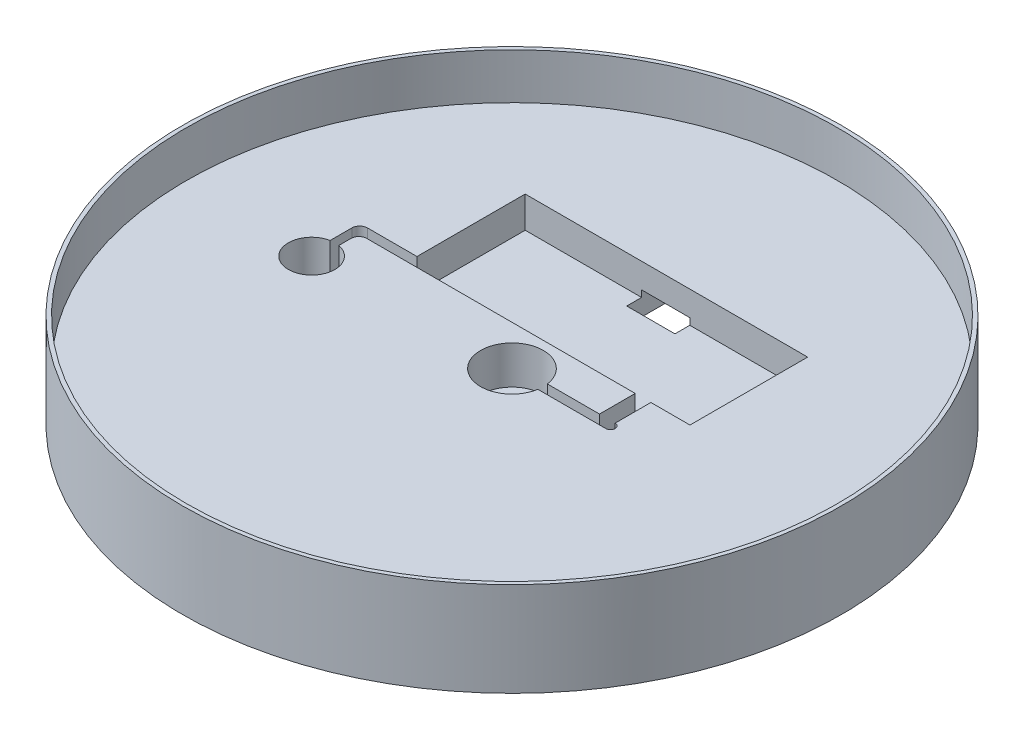
SolidWorks part; units mm, degrees
ref_plane "Front Plane" through (0, 0, 0) normal (0, 0, 1) x (1, 0, 0)
ref_plane "Top Plane" through (0, 0, 0) normal (0, 1, 0) x (1, 0, 0)
ref_plane "Right Plane" through (0, 0, 0) normal (1, 0, 0) x (0, 0, -1)
sketch "Sketch1" plane through (0, 0, 0) normal (0, 1, 0) x (1, 0, 0)
  circle A0 centre (0, 0) radius 266.7
extrude "Boss-Extrude1" add sketch "Sketch1" along normal blind 76.2
sketch "Sketch2" plane through (0, 76.2, 0) normal (0, 1, 0) x (1, 0, 0)
  circle A0 centre (0, 0) radius 263.525
extrude "Cut-Extrude1" cut sketch "Sketch2" against normal blind 37.084
sketch "Sketch3" plane through (0, 39.116, 0) normal (0, 1, 0) x (1, 0, 0)
  circle A0 centre (0, 0) radius 25.4
extrude "Cut-Extrude2" cut sketch "Sketch3" against normal blind 30.988
sketch "Sketch4" plane through (0, 39.116, 0) normal (0, 1, 0) x (1, 0, 0)
  line L0 (3.81, -0.2983) -> (80.01, -0.2983) construction
  line L1 (0, 3.5117) -> (76.2, 3.5117) construction
  line L2 (0, 3.5117) -> (0, -4.1083) construction
  line L3 (0, -4.1083) -> (76.2, -4.1083) construction
  line L4 (76.2, 3.5117) -> (76.2, -4.1083) construction
  line L5 (3.81, 3.5117) -> (80.01, 3.5117)
  line L6 (3.81, -4.1083) -> (80.01, -4.1083)
  line L7 (0, 3.5117) -> (0, -4.1083) construction
  arc A0 (3.81, 3.5117) -> (3.81, -4.1083) centre (3.81, -0.2983) ccw
  arc A1 (80.01, -4.1083) -> (80.01, 3.5117) centre (80.01, -0.2983) ccw
  point P6 (41.91, -0.2983)
extrude "Cut-Extrude3" cut sketch "Sketch4" against normal through all
sketch "Sketch15" plane through (0, 39.116, 0) normal (0, 1, 0) x (1, 0, 0)
  line L1 (-156.3248, 16.1533) -> (-156.3248, 18.4792)
  line L3 (-163.3516, 16.1533) -> (-163.3516, 18.4792)
  line L4 (-156.3248, 18.4792) -> (-163.3516, 18.4792)
  circle A0 centre (0, 0) radius 177.8 construction
  circle A1 centre (-159.4109, -0.0658) radius 16.9418 construction
  arc A2 (-163.3516, 16.1533) -> (-156.3248, 16.1533) centre (-159.8382, -2.3115) ccw
  point P6 (-159.8382, -2.3115)
extrude "Cut-Extrude12" cut sketch "Sketch15" against normal blind 27.94
sketch "Sketch19" plane through (0, 39.116, 0) normal (0, 1, 0) x (1, 0, 0)
  line L0 (80.01, 3.5117) -> (80.01, 32.4082)
  line L1 (-116.966, 32.4082) -> (67.31, 32.4082)
  line L2 (111.634, 32.4082) -> (111.634, 127.6582)
  line L3 (111.634, 127.6582) -> (-116.966, 127.6582)
  line L4 (-116.966, 127.6582) -> (-116.966, 32.4082)
  line L5 (80.01, 32.4082) -> (111.634, 32.4082)
  line L6 (67.31, 32.4082) -> (67.31, 3.5117)
  line L7 (80.01, 3.5117) -> (25.1561, 3.5117) construction
  line L8 (67.31, 3.5117) -> (80.01, 3.5117)
  circle A0 centre (0, 0) radius 263.525 construction
  circle A1 centre (0, 0) radius 177.7946 construction
extrude "Cut-Extrude13" cut sketch "Sketch19" against normal blind 25.4
sketch "Sketch20" plane through (0, 39.116, 0) normal (0, 1, 0) x (1, 0, 0)
  line L0 (-116.966, 32.4082) -> (-149.9748, 32.4082)
  line L1 (-156.3248, 26.0582) -> (-156.3248, 18.4792)
  line L2 (-156.3248, 18.4792) -> (-163.3516, 18.4792)
  line L3 (-163.3516, 18.4792) -> (-163.3516, 33.7217)
  line L4 (-157.0016, 40.0717) -> (-116.966, 40.0717)
  line L5 (-116.966, 127.6582) -> (-116.966, 32.4082) construction
  line L6 (-116.966, 40.0717) -> (-116.966, 32.4082)
  arc A0 (-157.0016, 40.0717) -> (-163.3516, 33.7217) centre (-157.0016, 33.7217) ccw
  arc A1 (-156.3248, 26.0582) -> (-149.9748, 32.4082) centre (-149.9748, 26.0582) cw
  dimension "D1" = 6.35
  dimension "D2" = 6.35
extrude "Cut-Extrude14" cut sketch "Sketch20" against normal blind 25.4
sketch "Sketch21" plane through (0, 0, 0) normal (0, -1, 0) x (-1, 0, 0)
  line L0 (22.7656, 115.6391) -> (-16.229, 115.6391) construction
  line L1 (-16.229, 115.6391) -> (-16.229, 283.8607)
  line L2 (-16.229, 283.8607) -> (22.7656, 283.8607)
  line L3 (22.7656, 283.8607) -> (22.7656, 115.6391)
  line L4 (22.7656, 115.6391) -> (-16.229, 115.6391)
extrude "Cut-Extrude15" cut sketch "Sketch21" against normal blind 19.05
sketch "Sketch22" plane through (0, 0, 0) normal (0, -1, 0) x (1, 0, 0)
  line L0 (16.229, -273.9885) -> (-22.7656, -273.9885) construction
  line L1 (-22.7656, -273.9885) -> (-22.7656, -115.6391)
  line L2 (-22.7656, -115.6391) -> (16.229, -115.6391)
  line L3 (16.229, -115.6391) -> (16.229, -273.9885)
  line L4 (16.229, -273.9885) -> (-22.7656, -273.9885)
  line L5 (0, 0) -> (-22.7656, -115.6391) construction
sketch "Sketch23" plane through (0, 39.116, 0) normal (0, 1, 0) x (1, 0, 0)
  line L0 (80.01, 3.5117) -> (80.01, 32.4082)
  line L1 (-116.966, 32.4082) -> (67.31, 32.4082)
  line L2 (111.634, 32.4082) -> (111.634, 127.6582)
  line L3 (111.634, 127.6582) -> (-116.966, 127.6582)
  line L4 (-116.966, 127.6582) -> (-116.966, 40.0717)
  line L5 (80.01, 32.4082) -> (111.634, 32.4082)
  line L6 (67.31, 32.4082) -> (67.31, 3.5117)
  line L7 (-116.966, 40.0717) -> (-157.0016, 40.0717)
  line L8 (67.31, 3.5117) -> (80.01, 3.5117)
  line L9 (-156.3248, 26.0582) -> (-156.3248, 18.4792)
  line L10 (-163.3516, 33.7217) -> (-163.3516, 18.4792)
  line L12 (-163.3516, 18.4792) -> (-156.3248, 18.4792)
  line L15 (-149.9748, 32.4082) -> (-116.966, 32.4082)
  circle A0 centre (0, 0) radius 263.525 construction
  circle A1 centre (0, 0) radius 177.7946 construction
  arc A2 (-149.9748, 32.4082) -> (-156.3248, 26.0582) centre (-149.9748, 26.0582) ccw
  arc A3 (-157.0016, 40.0717) -> (-163.3516, 33.7217) centre (-157.0016, 33.7217) ccw
  dimension "D1" = 6.35
  dimension "D2" = 6.35
sketch "Sketch24" plane through (0, 8.128, 0) normal (0, 1, 0) x (1, 0, 0)
  circle A0 centre (0, 0) radius 25.4
